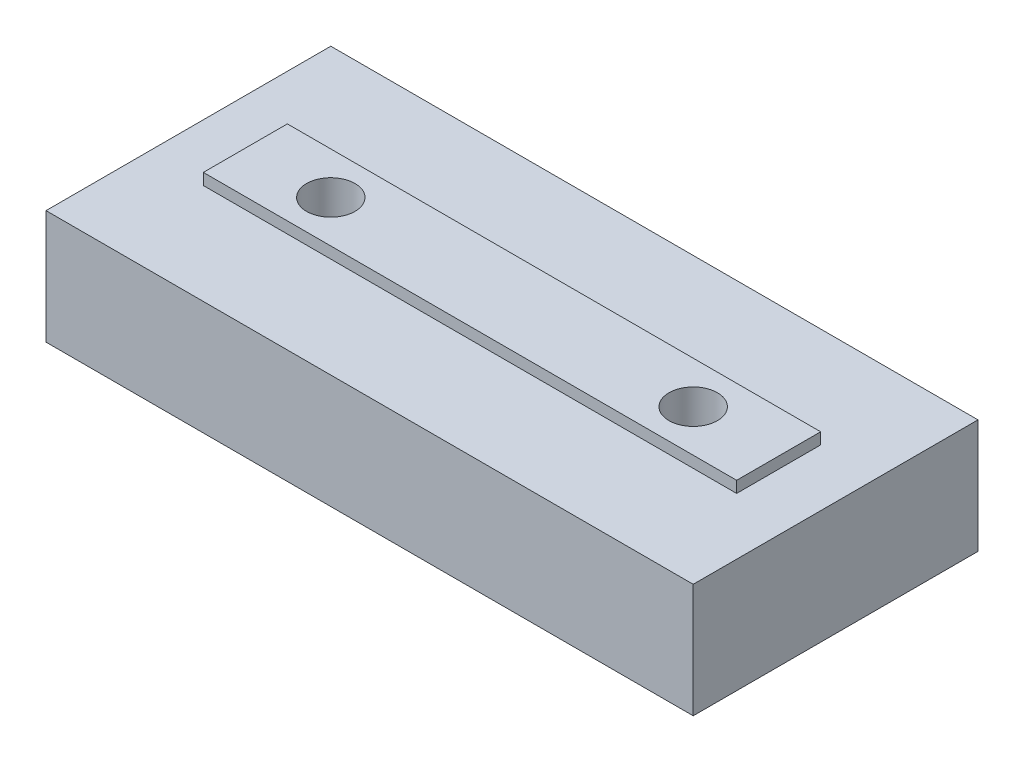
SolidWorks part; units mm, degrees
ref_plane "Front Plane" through (0, 0, 0) normal (0, 0, 1) x (1, 0, 0)
ref_plane "Top Plane" through (0, 0, 0) normal (0, 1, 0) x (1, 0, 0)
ref_plane "Right Plane" through (0, 0, 0) normal (1, 0, 0) x (0, 0, -1)
sketch "Sketch1" plane through (0, 0, 0) normal (0, 1, 0) x (1, 0, 0)
  line L1 (-15.0702, 8.0763) -> (30.3798, 8.0763)
  line L2 (-15.0702, 8.0763) -> (-15.0702, -11.9237)
  line L3 (-15.0702, -11.9237) -> (30.3798, -11.9237)
  line L4 (30.3798, 8.0763) -> (30.3798, -11.9237)
extrude "Boss-Extrude1" add sketch "Sketch1" along normal blind 8 contours L1 L4 L3 L2
sketch "Sketch2" plane through (0, 8, 0) normal (0, 1, 0) x (1, 0, 0)
  line L0 (-15.0702, -1.9237) -> (30.3798, -1.9237) construction
  line L2 (-15.0702, 8.0763) -> (-15.0702, -11.9237) construction
  line L4 (-11.0702, 1.0263) -> (-11.0702, -4.8737)
  line L5 (-11.0702, 1.0263) -> (26.3798, 1.0263)
  line L7 (-11.0702, -4.8737) -> (26.3798, -4.8737)
  line L8 (26.3798, 1.0263) -> (26.3798, -4.8737)
  line L9 (30.3798, 8.0763) -> (30.3798, -11.9237) construction
  point P4 (0, 0)
  point P7 (0, 0)
  point P13 (26.3798, -1.9237)
  point P14 (-11.0702, -1.9237)
  dimension "D1" = 5.9
  dimension "D2" = 4
  dimension "D3" = 4
extrude "Boss-Extrude2" add sketch "Sketch2" along normal blind 0.8 contours L7 L8 L5 L4
ref_plane "Plane1" through (7.6548, 0, 0) normal (-1, 0, 0) x (0, 0, 1)
hole_wizard "M3 Clearance Hole1" positions "Sketch3" profile "Sketch4" hole size "M3" standard "DIN" end condition through all
sketch "Sketch3" plane through (0, 0, 0) normal (0, -1, 0) x (-1, 0, 0)
  line L1 (-7.6548, -9.9397) -> (-7.6548, 9.9397) construction
  line L4 (-30.3798, -1.9237) -> (15.0702, -1.9237) construction
  line L5 (-30.3798, 8.0763) -> (-30.3798, -11.9237) construction
  line L6 (15.0702, 8.0763) -> (15.0702, -11.9237) construction
  point P0 (-20.3798, -1.9237)
  point P12 (5.0702, -1.9237)
  point P26 (0, 0)
  dimension "D1" = 10
sketch "Sketch4" plane through (20.3798, 0, 1.9237) normal (1, 0, 0) x (0, 0, -1)
  line L0 (0, 0) -> (0, 8.8)
  line L1 (0, 8.8) -> (1.7, 8.8)
  line L2 (1.7, 8.8) -> (1.7, 0)
  line L5 (1.7, 0) -> (0, 0)
  line L11 (0, -6.35) -> (0, 107.95) construction
  dimension "Thru Hole Dia." = 3.4
  dimension "Thru Hole Depth" = 8.8
